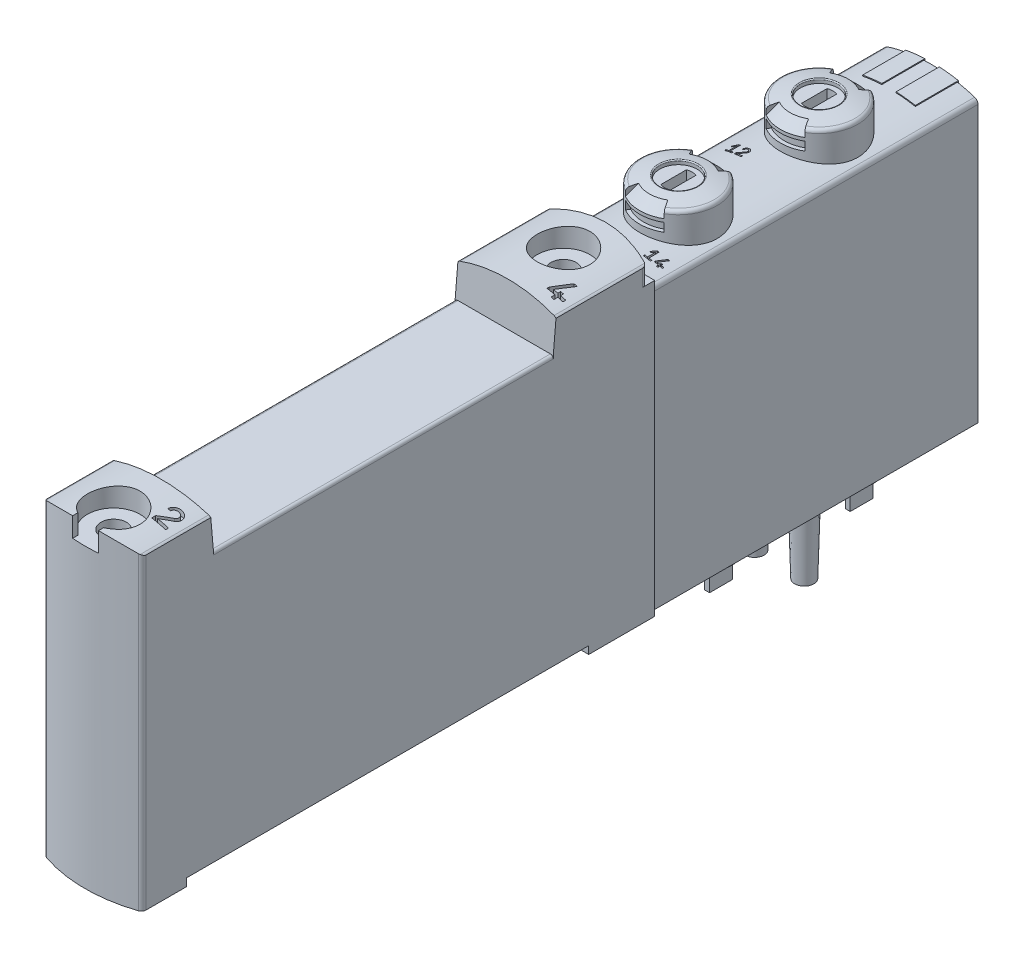
SolidWorks part; units mm, degrees
ref_plane "Front Plane" through (0, 0, 0) normal (0, 0, 1) x (1, 0, 0)
ref_plane "Top Plane" through (0, 0, 0) normal (0, 1, 0) x (1, 0, 0)
ref_plane "Right Plane" through (0, 0, 0) normal (1, 0, 0) x (0, 0, -1)
ref_plane "Plane1" through (0, 0, -23.2) normal (0, 0, 1) x (1, 0, 0)
sketch "Sketch1" plane through (0, 0, -23.2) normal (0, 0, 1) x (1, 0, 0)
  line L0 (-4.9, 29.2163) -> (-4.9, 0)
  line L1 (-4.9, 0) -> (4.9, 0)
  line L2 (4.9, 0) -> (4.9, 29.2163)
  arc A0 (4.9, 29.2163) -> (4.5517, 29.6927) centre (4.4, 29.2163) ccw
  arc A1 (4.5517, 29.6927) -> (-4.5517, 29.6927) centre (0, 15.4) ccw
  arc A2 (-4.5517, 29.6927) -> (-4.9, 29.2163) centre (-4.4, 29.2163) ccw
extrude "Boss-Extrude1" add sketch "Sketch1" along normal blind 34
ref_plane "Plane2" through (0, 0, 0) normal (1, 0, 0) x (0, 0, -1)
sketch "Sketch2" plane through (0, 0, 0) normal (1, 0, 0) x (0, 0, -1)
  line L0 (-10.88, 0.4) -> (-10.88, 0)
  line L1 (-10.88, 0) -> (23.22, 0)
  line L2 (23.22, 0) -> (23.22, 0.4)
  line L3 (23.22, 0.4) -> (-10.88, 0.4)
extrude "Cut-Extrude1" cut sketch "Sketch2" against normal blind 6 and the other way blind 6
ref_plane "Plane3" through (0, 0, 0) normal (0, 1, 0) x (1, 0, 0)
sketch "Sketch3" plane through (0, 0, 0) normal (0, 1, 0) x (1, 0, 0)
  line L0 (-3.15, 2.4653) -> (-3.15, -2.4653)
  line L1 (3.15, -2.4653) -> (3.15, 2.4653)
  arc A0 (-3.15, -2.4653) -> (3.15, -2.4653) centre (0, 0) ccw
  arc A1 (3.15, 2.4653) -> (-3.15, 2.4653) centre (0, 0) ccw
extrude "Cut-Extrude2" cut sketch "Sketch3" along normal blind 1.9
ref_plane "Plane4" through (0, 0, 0) normal (0, 1, 0) x (1, 0, 0)
sketch "Sketch4" plane through (0, 0, 0) normal (0, 1, 0) x (1, 0, 0)
  line L0 (-3.15, 17.1653) -> (-3.15, 12.2347)
  line L1 (3.15, 12.2347) -> (3.15, 17.1653)
  arc A0 (-3.15, 12.2347) -> (3.15, 12.2347) centre (0, 14.7) ccw
  arc A1 (3.15, 17.1653) -> (-3.15, 17.1653) centre (0, 14.7) ccw
extrude "Cut-Extrude3" cut sketch "Sketch4" along normal blind 1.9
ref_plane "Plane5" through (0, 0, 0) normal (1, 0, 0) x (0, 0, -1)
sketch "Sketch5" plane through (0, 0, 0) normal (1, 0, 0) x (0, 0, -1)
  line L0 (0, 2.1) -> (3.05, 2.1)
  line L1 (3.05, 2.1) -> (3.05, 1.1)
  line L2 (3.05, 1.1) -> (2.25, 1.1)
  line L3 (2.25, 1.1) -> (2.25, -1.4)
  line L4 (2.25, -1.4) -> (2.65, -1.4)
  line L5 (2.65, -1.4) -> (2.65, -1.72)
  line L6 (2.65, -1.72) -> (2.4306, -2.1)
  line L7 (2.4306, -2.1) -> (0, -2.1)
  line L8 (0, -2.1) -> (0, 2.1)
  line L9 (0, -2.1) -> (0, 2.1) construction
revolve "Revolve1" add sketch "Sketch5" angle 360 about L9 reverse direction yes
ref_plane "Plane6" through (0, 0, 0) normal (1, 0, 0) x (0, 0, -1)
sketch "Sketch6" plane through (0, 0, 0) normal (1, 0, 0) x (0, 0, -1)
  line L0 (14.7, 2.1) -> (17.75, 2.1)
  line L1 (17.75, 2.1) -> (17.75, 1.1)
  line L2 (17.75, 1.1) -> (16.95, 1.1)
  line L3 (16.95, 1.1) -> (16.95, -1.4)
  line L4 (16.95, -1.4) -> (17.35, -1.4)
  line L5 (17.35, -1.4) -> (17.35, -1.72)
  line L6 (17.35, -1.72) -> (17.1306, -2.1)
  line L7 (17.1306, -2.1) -> (14.7, -2.1)
  line L8 (14.7, -2.1) -> (14.7, 2.1)
  line L9 (14.7, -2.1) -> (14.7, 2.1) construction
revolve "Revolve2" add sketch "Sketch6" angle 360 about L9 reverse direction yes
ref_plane "Plane7" through (0, 0, -7.35) normal (0, 0, 1) x (1, 0, 0)
sketch "Sketch7" plane through (0, 0, -7.35) normal (0, 0, 1) x (1, 0, 0)
  line L0 (2.6, 0.4) -> (3.8, 0.4)
  line L1 (3.8, 0.4) -> (3.6, -6.9)
  line L2 (2.6, -7.0623) -> (2.6, 0.4)
  line L3 (2.6, -7.0623) -> (2.6, 0.4) construction
  arc A0 (3.6, -6.9) -> (2.6, -7.0623) centre (2.6, -3.9) cw
revolve "Revolve3" add sketch "Sketch7" angle 360 about L3 reverse direction yes
ref_plane "Plane8" through (0, 0, -7.35) normal (0, 0, 1) x (1, 0, 0)
sketch "Sketch8" plane through (0, 0, -7.35) normal (0, 0, 1) x (1, 0, 0)
  line L0 (-2.6, 0.4) -> (-1.4, 0.4)
  line L1 (-1.4, 0.4) -> (-1.6, -6.9)
  line L2 (-2.6, -7.0623) -> (-2.6, 0.4)
  line L3 (-2.6, -7.0623) -> (-2.6, 0.4) construction
  arc A0 (-1.6, -6.9) -> (-2.6, -7.0623) centre (-2.6, -3.9) cw
revolve "Revolve4" add sketch "Sketch8" angle 360 about L3 reverse direction yes
ref_plane "Plane9" through (0, -2.1, 0) normal (0, -1, 0) x (-1, 0, 0)
sketch "Sketch9" plane through (0, -2.1, 0) normal (0, -1, 0) x (-1, 0, 0)
  line L0 (-1.25, -1.2) -> (-0.75, -1.2)
  line L1 (-0.75, -1.2) -> (-0.75, 1.2)
  line L2 (-0.75, 1.2) -> (-1.25, 1.2)
  line L3 (-1.25, 1.2) -> (-1.25, -1.2)
extrude "Boss-Extrude2" add sketch "Sketch9" along normal blind 2.5
ref_plane "Plane10" through (0, -2.1, 0) normal (0, -1, 0) x (-1, 0, 0)
sketch "Sketch10" plane through (0, -2.1, 0) normal (0, -1, 0) x (-1, 0, 0)
  line L0 (0.75, -1.2) -> (1.25, -1.2)
  line L1 (1.25, -1.2) -> (1.25, 1.2)
  line L2 (1.25, 1.2) -> (0.75, 1.2)
  line L3 (0.75, 1.2) -> (0.75, -1.2)
extrude "Boss-Extrude3" add sketch "Sketch10" along normal blind 2.5
ref_plane "Plane11" through (0, -2.1, 0) normal (0, -1, 0) x (-1, 0, 0)
sketch "Sketch11" plane through (0, -2.1, 0) normal (0, -1, 0) x (-1, 0, 0)
  line L0 (-1.25, 13.5) -> (-0.75, 13.5)
  line L1 (-0.75, 13.5) -> (-0.75, 15.9)
  line L2 (-0.75, 15.9) -> (-1.25, 15.9)
  line L3 (-1.25, 15.9) -> (-1.25, 13.5)
extrude "Boss-Extrude4" add sketch "Sketch11" along normal blind 2.5
ref_plane "Plane12" through (0, -2.1, 0) normal (0, -1, 0) x (-1, 0, 0)
sketch "Sketch12" plane through (0, -2.1, 0) normal (0, -1, 0) x (-1, 0, 0)
  line L0 (0.75, 13.5) -> (1.25, 13.5)
  line L1 (1.25, 13.5) -> (1.25, 15.9)
  line L2 (1.25, 15.9) -> (0.75, 15.9)
  line L3 (0.75, 15.9) -> (0.75, 13.5)
extrude "Boss-Extrude5" add sketch "Sketch12" along normal blind 2.5
ref_plane "Plane13" through (0, 0, 0) normal (1, 0, 0) x (0, 0, -1)
sketch "Sketch13" plane through (0, 0, 0) normal (1, 0, 0) x (0, 0, -1)
  line L0 (-3.2, 33.13) -> (-1.25, 33.13)
  line L1 (-1.25, 33.13) -> (-1.25, 33.4583)
  line L2 (0.85, 32.8364) -> (0.85, 28.4)
  line L3 (0.85, 28.4) -> (-3.2, 28.4)
  line L4 (-3.2, 28.4) -> (-3.2, 33.13)
  line L5 (-3.2, 28.4) -> (-3.2, 33.7) construction
  arc A0 (-1.25, 33.4583) -> (-1.1362, 33.5574) centre (-1.15, 33.4583) cw
  arc A1 (-1.1362, 33.5574) -> (0.55, 33.2237) centre (-3.2, 18.7) cw
  arc A2 (0.55, 33.2237) -> (0.85, 32.8364) centre (0.45, 32.8364) cw
revolve "Revolve5" add sketch "Sketch13" angle 360 about L5 reverse direction yes
ref_plane "Plane14" through (0, 0, 0) normal (1, 0, 0) x (0, 0, -1)
sketch "Sketch14" plane through (0, 0, 0) normal (1, 0, 0) x (0, 0, -1)
  line L0 (11.5, 33.13) -> (13.45, 33.13)
  line L1 (13.45, 33.13) -> (13.45, 33.4583)
  line L2 (15.55, 32.8364) -> (15.55, 28.4)
  line L3 (15.55, 28.4) -> (11.5, 28.4)
  line L4 (11.5, 28.4) -> (11.5, 33.13)
  line L5 (11.5, 28.4) -> (11.5, 33.7) construction
  arc A0 (13.45, 33.4583) -> (13.5638, 33.5574) centre (13.55, 33.4583) cw
  arc A1 (13.5638, 33.5574) -> (15.25, 33.2237) centre (11.5, 18.7) cw
  arc A2 (15.25, 33.2237) -> (15.55, 32.8364) centre (15.15, 32.8364) cw
revolve "Revolve6" add sketch "Sketch14" angle 360 about L5 reverse direction yes
ref_plane "Plane15" through (0, 0, 0) normal (1, 0, 0) x (0, 0, -1)
sketch "Sketch15" plane through (0, 0, 0) normal (1, 0, 0) x (0, 0, -1)
  line L0 (-0.47, 33.7) -> (0.9, 32.33)
  line L1 (0.9, 32.33) -> (0.9, 32.05)
  line L2 (0.9, 32.05) -> (0.45, 32.05)
  line L3 (0.45, 32.05) -> (0.45, 31.15)
  line L4 (0.45, 31.15) -> (0.9, 31.15)
  line L5 (0.9, 31.15) -> (0.9, 30.5)
  line L6 (0.9, 30.5) -> (1.3, 30.5)
  line L7 (1.3, 30.5) -> (1.3, 33.7)
  line L8 (1.3, 33.7) -> (-0.47, 33.7)
  line L9 (-3.2, 30.5) -> (-3.2, 33.7) construction
revolve "Cut-Revolve1" cut sketch "Sketch15" angle 30 about L9 other way angle 30 reverse direction yes
ref_plane "Plane16" through (0, 0, 0) normal (1, 0, 0) x (0, 0, -1)
sketch "Sketch16" plane through (0, 0, 0) normal (1, 0, 0) x (0, 0, -1)
  line L0 (-7.7, 30.5) -> (-7.3, 30.5)
  line L1 (-7.3, 30.5) -> (-7.3, 31.15)
  line L2 (-7.3, 31.15) -> (-6.85, 31.15)
  line L3 (-6.85, 31.15) -> (-6.85, 32.05)
  line L4 (-6.85, 32.05) -> (-7.3, 32.05)
  line L5 (-7.3, 32.05) -> (-7.3, 32.33)
  line L6 (-7.3, 32.33) -> (-5.93, 33.7)
  line L7 (-5.93, 33.7) -> (-7.7, 33.7)
  line L8 (-7.7, 33.7) -> (-7.7, 30.5)
  line L9 (-3.2, 33.7) -> (-3.2, 30.5) construction
revolve "Cut-Revolve2" cut sketch "Sketch16" angle 30 about L9 other way angle 30 reverse direction yes
ref_plane "Plane17" through (0, 33.13, 0) normal (0, 1, 0) x (1, 0, 0)
sketch "Sketch17" plane through (0, 33.13, 0) normal (0, 1, 0) x (1, 0, 0)
  line L0 (0.5, -4.5344) -> (0.5, -1.8656)
  line L1 (-0.5, -1.8656) -> (-0.5, -4.5344)
  arc A0 (-0.5, -4.5344) -> (0.5, -4.5344) centre (0, -3.2) ccw
  arc A1 (0.5, -1.8656) -> (-0.5, -1.8656) centre (0, -3.2) ccw
extrude "Cut-Extrude4" cut sketch "Sketch17" against normal blind 1.7
ref_plane "Plane18" through (0, 0, 0) normal (1, 0, 0) x (0, 0, -1)
sketch "Sketch18" plane through (0, 0, 0) normal (1, 0, 0) x (0, 0, -1)
  line L0 (14.23, 33.7) -> (15.6, 32.33)
  line L1 (15.6, 32.33) -> (15.6, 32.05)
  line L2 (15.6, 32.05) -> (15.15, 32.05)
  line L3 (15.15, 32.05) -> (15.15, 31.15)
  line L4 (15.15, 31.15) -> (15.6, 31.15)
  line L5 (15.6, 31.15) -> (15.6, 30.5)
  line L6 (15.6, 30.5) -> (16, 30.5)
  line L7 (16, 30.5) -> (16, 33.7)
  line L8 (16, 33.7) -> (14.23, 33.7)
  line L9 (11.5, 30.5) -> (11.5, 33.7) construction
revolve "Cut-Revolve3" cut sketch "Sketch18" angle 30 about L9 other way angle 30 reverse direction yes
ref_plane "Plane19" through (0, 0, 0) normal (1, 0, 0) x (0, 0, -1)
sketch "Sketch19" plane through (0, 0, 0) normal (1, 0, 0) x (0, 0, -1)
  line L0 (7, 30.5) -> (7.4, 30.5)
  line L1 (7.4, 30.5) -> (7.4, 31.15)
  line L2 (7.4, 31.15) -> (7.85, 31.15)
  line L3 (7.85, 31.15) -> (7.85, 32.05)
  line L4 (7.85, 32.05) -> (7.4, 32.05)
  line L5 (7.4, 32.05) -> (7.4, 32.33)
  line L6 (7.4, 32.33) -> (8.77, 33.7)
  line L7 (8.77, 33.7) -> (7, 33.7)
  line L8 (7, 33.7) -> (7, 30.5)
  line L9 (11.5, 33.7) -> (11.5, 30.5) construction
revolve "Cut-Revolve4" cut sketch "Sketch19" angle 30 about L9 other way angle 30 reverse direction yes
ref_plane "Plane20" through (0, 33.13, 0) normal (0, 1, 0) x (1, 0, 0)
sketch "Sketch20" plane through (0, 33.13, 0) normal (0, 1, 0) x (1, 0, 0)
  line L0 (0.5, 10.1656) -> (0.5, 12.8344)
  line L1 (-0.5, 12.8344) -> (-0.5, 10.1656)
  arc A0 (-0.5, 10.1656) -> (0.5, 10.1656) centre (0, 11.5) ccw
  arc A1 (0.5, 12.8344) -> (-0.5, 12.8344) centre (0, 11.5) ccw
extrude "Cut-Extrude5" cut sketch "Sketch20" against normal blind 1.7
ref_plane "Plane21" through (0, 0, -23.3) normal (0, 0, 1) x (1, 0, 0)
sketch "Sketch21" plane through (0, 0, -23.3) normal (0, 0, 1) x (1, 0, 0)
  line L0 (0.75, 30.4814) -> (0.75, 27)
  line L1 (0.75, 27) -> (2.75, 27)
  line L2 (2.75, 27) -> (2.75, 30.2475)
  arc A0 (2.75, 30.2475) -> (0.75, 30.4814) centre (0, 15.4) ccw
extrude "Boss-Extrude6" add sketch "Sketch21" along normal blind 4.5
ref_plane "Plane22" through (0, 0, -23.3) normal (0, 0, 1) x (1, 0, 0)
sketch "Sketch22" plane through (0, 0, -23.3) normal (0, 0, 1) x (1, 0, 0)
  line L0 (-2.75, 30.2475) -> (-2.75, 27)
  line L1 (-2.75, 27) -> (-0.75, 27)
  line L2 (-0.75, 27) -> (-0.75, 30.4814)
  arc A0 (-0.75, 30.4814) -> (-2.75, 30.2475) centre (0, 15.4) ccw
extrude "Boss-Extrude7" add sketch "Sketch22" along normal blind 4.5
ref_plane "Plane23" through (0, 0, 0) normal (0, 1, 0) x (1, 0, 0)
sketch "Sketch23" plane through (0, 0, 0) normal (0, 1, 0) x (1, 0, 0)
  line L0 (5.125, -63.9426) -> (5.125, -10.8)
  line L1 (5.125, -10.8) -> (-5.125, -10.8)
  line L2 (-5.125, -10.8) -> (-5.125, -63.9426)
  arc A0 (-5.125, -63.9426) -> (-4.7845, -64.4165) centre (-4.625, -63.9426) ccw
  arc A1 (-4.7845, -64.4165) -> (4.7845, -64.4165) centre (0, -50.2) ccw
  arc A2 (4.7845, -64.4165) -> (5.125, -63.9426) centre (4.625, -63.9426) ccw
extrude "Boss-Extrude8" add sketch "Sketch23" along normal blind 33.1
ref_plane "Plane24" through (0, 0, 0) normal (1, 0, 0) x (0, 0, -1)
sketch "Sketch24" plane through (0, 0, 0) normal (1, 0, 0) x (0, 0, -1)
  line L0 (-57.7749, 38.9) -> (-56.9, 28.9)
  line L1 (-56.9, 28.9) -> (-21.4, 28.9)
  line L2 (-21.4, 28.9) -> (-20.5251, 38.9)
  line L3 (-20.5251, 38.9) -> (-57.7749, 38.9)
extrude "Cut-Extrude6" cut sketch "Sketch24" against normal blind 10 and the other way blind 10
ref_plane "Plane25" through (0, 30.4, 0) normal (0, 1, 0) x (1, 0, 0)
sketch "Sketch25" plane through (0, 30.4, 0) normal (0, 1, 0) x (1, 0, 0)
  line L0 (-5.125, -8.8) -> (-5.125, -12.0574)
  line L1 (5.125, -12.0574) -> (5.125, -8.8)
  line L2 (5.125, -8.8) -> (-5.125, -8.8)
  arc A0 (-5.125, -12.0574) -> (-4.7845, -11.5835) centre (-4.625, -12.0574) cw
  arc A1 (-4.7845, -11.5835) -> (4.7845, -11.5835) centre (0, -25.8) cw
  arc A2 (4.7845, -11.5835) -> (5.125, -12.0574) centre (4.625, -12.0574) cw
extrude "Cut-Extrude7" cut sketch "Sketch25" along normal blind 10
ref_plane "Plane26" through (0, 0, 0) normal (1, 0, 0) x (0, 0, -1)
sketch "Sketch26" plane through (0, 0, 0) normal (1, 0, 0) x (0, 0, -1)
  line L0 (-59.7, -0.2) -> (-17.7, -0.2)
  line L1 (-17.7, -0.2) -> (-17.7, 0.8)
  line L2 (-17.7, 0.8) -> (-59.7, 0.8)
  line L3 (-59.7, 0.8) -> (-59.7, -0.2)
extrude "Cut-Extrude8" cut sketch "Sketch26" against normal blind 10 and the other way blind 10
ref_plane "Plane27" through (0, 0, 10.8) normal (0, 0, 1) x (1, 0, 0)
sketch "Sketch27" plane through (0, 0, 10.8) normal (0, 0, 1) x (1, 0, 0)
  line L0 (-5.25, 35.1) -> (-5.25, 31.7999)
  line L1 (5.25, 31.7999) -> (5.25, 35.1)
  line L2 (5.25, 35.1) -> (-5.25, 35.1)
  arc A0 (-5.25, 31.7999) -> (-4.9138, 32.2723) centre (-4.75, 31.7999) cw
  arc A1 (-4.9138, 32.2723) -> (4.9138, 32.2723) centre (0, 18.1) cw
  arc A2 (4.9138, 32.2723) -> (5.25, 31.7999) centre (4.75, 31.7999) cw
extrude "Cut-Extrude9" cut sketch "Sketch27" along normal blind 55
ref_plane "Plane28" through (0, 0, 21.4) normal (0, 0, 1) x (1, 0, 0)
sketch "Sketch28" plane through (0, 0, 21.4) normal (0, 0, 1) x (1, 0, 0)
  line L0 (-4.825, 28.9) -> (4.825, 28.9)
  line L1 (5.125, 28.6) -> (5.125, 33.6)
  line L2 (5.125, 33.6) -> (-5.125, 33.6)
  line L3 (-5.125, 33.6) -> (-5.125, 28.6)
  arc A0 (-5.125, 28.6) -> (-4.825, 28.9) centre (-4.825, 28.6) cw
  arc A1 (4.825, 28.9) -> (5.125, 28.6) centre (4.825, 28.6) cw
extrude "Cut-Extrude10" cut sketch "Sketch28" along normal blind 35.5
ref_plane "Plane29" through (0, 33.1, 0) normal (0, 1, 0) x (1, 0, 0)
sketch "Sketch29" plane through (0, 33.1, 0) normal (0, 1, 0) x (1, 0, 0)
  line L0 (-1.35, -64.5958) -> (-1.35, -66)
  line L1 (-1.35, -66) -> (1.35, -66)
  line L2 (1.35, -66) -> (1.35, -64.5958)
  arc A0 (1.35, -64.5958) -> (-1.35, -64.5958) centre (0, -62.2) ccw
extrude "Cut-Extrude11" cut sketch "Sketch29" against normal blind 2.1 and the other way blind 2.1
ref_plane "Plane30" through (0, 0, 0) normal (1, 0, 0) x (0, 0, -1)
sketch "Sketch30" plane through (0, 0, 0) normal (1, 0, 0) x (0, 0, -1)
  line L0 (-62.2, 31) -> (-60.875, 31)
  line L1 (-60.875, 31) -> (-60.875, 0)
  line L2 (-60.875, 0) -> (-62.2, 0)
  line L3 (-62.2, 0) -> (-62.2, 31)
  line L4 (-62.2, 0) -> (-62.2, 31) construction
revolve "Cut-Revolve5" cut sketch "Sketch30" angle 360 about L4 reverse direction yes
ref_plane "Plane31" through (0, 0, 0) normal (1, 0, 0) x (0, 0, -1)
sketch "Sketch31" plane through (0, 0, 0) normal (1, 0, 0) x (0, 0, -1)
  line L0 (-15.2, 33.2) -> (-12.45, 33.2)
  line L1 (-12.45, 33.2) -> (-12.45, 31)
  line L2 (-12.45, 31) -> (-13.875, 31)
  line L3 (-13.875, 31) -> (-13.875, 0)
  line L4 (-13.875, 0) -> (-15.2, 0)
  line L5 (-15.2, 0) -> (-15.2, 33.2)
  line L6 (-15.2, 0) -> (-15.2, 33.2) construction
revolve "Cut-Revolve6" cut sketch "Sketch31" angle 360 about L6 reverse direction yes
ref_plane "Plane32" through (0, 0, 0) normal (1, 0, 0) x (0, 0, -1)
sketch "Sketch32" plane through (0, 0, 0) normal (1, 0, 0) x (0, 0, -1)
  line L0 (-40.2, 9.8) -> (-38.1, 9.8)
  line L1 (-38.1, 9.8) -> (-38.1, 1.8)
  line L2 (-38.1, 1.8) -> (-37.4, 1.8)
  line L3 (-37.4, 1.8) -> (-37.4, 0.8)
  line L4 (-37.4, 0.8) -> (-40.2, 0.8)
  line L5 (-40.2, 0.8) -> (-40.2, 9.8)
  line L6 (-40.2, 0.8) -> (-40.2, 9.8) construction
revolve "Cut-Revolve7" cut sketch "Sketch32" angle 360 about L6 reverse direction yes
ref_plane "Plane33" through (-1.55, 0, 0) normal (1, 0, 0) x (0, 0, -1)
sketch "Sketch33" plane through (-1.55, 0, 0) normal (1, 0, 0) x (0, 0, -1)
  line L0 (-29.1, 9.8) -> (-27, 9.8)
  line L1 (-27, 9.8) -> (-27, 1.8)
  line L2 (-27, 1.8) -> (-26.3, 1.8)
  line L3 (-26.3, 1.8) -> (-26.3, 0.8)
  line L4 (-26.3, 0.8) -> (-29.1, 0.8)
  line L5 (-29.1, 0.8) -> (-29.1, 9.8)
  line L6 (-29.1, 0.8) -> (-29.1, 9.8) construction
revolve "Cut-Revolve8" cut sketch "Sketch33" angle 360 about L6 reverse direction yes
ref_plane "Plane34" through (-1.55, 0, 0) normal (1, 0, 0) x (0, 0, -1)
sketch "Sketch34" plane through (-1.55, 0, 0) normal (1, 0, 0) x (0, 0, -1)
  line L0 (-46.1, 9.8) -> (-44, 9.8)
  line L1 (-44, 9.8) -> (-44, 1.8)
  line L2 (-44, 1.8) -> (-43.3, 1.8)
  line L3 (-43.3, 1.8) -> (-43.3, 0.8)
  line L4 (-43.3, 0.8) -> (-46.1, 0.8)
  line L5 (-46.1, 0.8) -> (-46.1, 9.8)
  line L6 (-46.1, 0.8) -> (-46.1, 9.8) construction
revolve "Cut-Revolve9" cut sketch "Sketch34" angle 360 about L6 reverse direction yes
ref_plane "Plane35" through (1.55, 0, 0) normal (1, 0, 0) x (0, 0, -1)
sketch "Sketch35" plane through (1.55, 0, 0) normal (1, 0, 0) x (0, 0, -1)
  line L0 (-34.3, 9.8) -> (-32.2, 9.8)
  line L1 (-32.2, 9.8) -> (-32.2, 1.8)
  line L2 (-32.2, 1.8) -> (-31.5, 1.8)
  line L3 (-31.5, 1.8) -> (-31.5, 0.8)
  line L4 (-31.5, 0.8) -> (-34.3, 0.8)
  line L5 (-34.3, 0.8) -> (-34.3, 9.8)
  line L6 (-34.3, 0.8) -> (-34.3, 9.8) construction
revolve "Cut-Revolve10" cut sketch "Sketch35" angle 360 about L6 reverse direction yes
ref_plane "Plane36" through (1.55, 0, 0) normal (1, 0, 0) x (0, 0, -1)
sketch "Sketch36" plane through (1.55, 0, 0) normal (1, 0, 0) x (0, 0, -1)
  line L0 (-51.3, 9.8) -> (-49.2, 9.8)
  line L1 (-49.2, 9.8) -> (-49.2, 1.8)
  line L2 (-49.2, 1.8) -> (-48.5, 1.8)
  line L3 (-48.5, 1.8) -> (-48.5, 0.8)
  line L4 (-48.5, 0.8) -> (-51.3, 0.8)
  line L5 (-51.3, 0.8) -> (-51.3, 9.8)
  line L6 (-51.3, 0.8) -> (-51.3, 9.8) construction
revolve "Cut-Revolve11" cut sketch "Sketch36" angle 360 about L6 reverse direction yes
ref_plane "Plane37" through (0, 33.1, 0) normal (0, 1, 0) x (1, 0, 0)
sketch "Sketch37" plane through (0, 33.1, 0) normal (0, 1, 0) x (1, 0, 0)
  line L0 (-3.3985, 5.738) -> (-3.2978, 5.6676)
  line L1 (-3.2978, 5.6676) -> (-3.075, 5.9858)
  line L2 (-3.075, 5.9858) -> (-3.075, 5.15)
  line L3 (-3.075, 5.15) -> (-3.375, 5.15)
  line L4 (-3.375, 5.15) -> (-3.375, 5)
  line L5 (-3.375, 5) -> (-2.625, 5)
  line L6 (-2.625, 5) -> (-2.625, 5.15)
  line L7 (-2.625, 5.15) -> (-2.925, 5.15)
  line L8 (-2.925, 5.15) -> (-2.925, 6.2)
  line L9 (-2.925, 6.2) -> (-3.075, 6.2)
  line L10 (-3.075, 6.2) -> (-3.3985, 5.738)
extrude "Cut-Extrude12" cut sketch "Sketch37" against normal blind 3.5 and the other way blind 3.5
ref_plane "Plane38" through (0, 33.1, 0) normal (0, 1, 0) x (1, 0, 0)
sketch "Sketch38" plane through (0, 33.1, 0) normal (0, 1, 0) x (1, 0, 0)
  line L0 (-2.3625, 5.8375) -> (-2.2125, 5.8375)
  line L1 (-1.8546, 5.6826) -> (-2.3625, 5.2057)
  line L2 (-2.3625, 5.2057) -> (-2.3625, 5)
  line L3 (-2.3625, 5) -> (-1.6375, 5)
  line L4 (-1.6375, 5) -> (-1.6375, 5.15)
  line L5 (-1.6375, 5.15) -> (-2.2027, 5.15)
  line L6 (-2.2027, 5.15) -> (-1.7519, 5.5732)
  arc A0 (-2.2125, 5.8375) -> (-1.8546, 5.6826) centre (-2, 5.8375) cw
  arc A1 (-1.7519, 5.5732) -> (-2.3625, 5.8375) centre (-2, 5.8375) ccw
extrude "Cut-Extrude13" cut sketch "Sketch38" against normal blind 3.5 and the other way blind 3.5
ref_plane "Plane39" through (0, 33.1, 0) normal (0, 1, 0) x (1, 0, 0)
sketch "Sketch39" plane through (0, 33.1, 0) normal (0, 1, 0) x (1, 0, 0)
  line L0 (2.1015, -8.262) -> (2.2022, -8.3324)
  line L1 (2.2022, -8.3324) -> (2.425, -8.0142)
  line L2 (2.425, -8.0142) -> (2.425, -8.85)
  line L3 (2.425, -8.85) -> (2.125, -8.85)
  line L4 (2.125, -8.85) -> (2.125, -9)
  line L5 (2.125, -9) -> (2.875, -9)
  line L6 (2.875, -9) -> (2.875, -8.85)
  line L7 (2.875, -8.85) -> (2.575, -8.85)
  line L8 (2.575, -8.85) -> (2.575, -7.8)
  line L9 (2.575, -7.8) -> (2.425, -7.8)
  line L10 (2.425, -7.8) -> (2.1015, -8.262)
extrude "Cut-Extrude14" cut sketch "Sketch39" against normal blind 3.5 and the other way blind 3.5
ref_plane "Plane40" through (0, 33.1, 0) normal (0, 1, 0) x (1, 0, 0)
sketch "Sketch40" plane through (0, 33.1, 0) normal (0, 1, 0) x (1, 0, 0)
  line L0 (3.085, -8.8) -> (3.5, -8.8)
  line L1 (3.5, -8.8) -> (3.5, -9)
  line L2 (3.5, -9) -> (3.65, -9)
  line L3 (3.65, -9) -> (3.65, -8.8)
  line L4 (3.65, -8.8) -> (3.915, -8.8)
  line L5 (3.915, -8.8) -> (3.915, -8.65)
  line L6 (3.915, -8.65) -> (3.65, -8.65)
  line L7 (3.65, -8.65) -> (3.65, -8.5)
  line L8 (3.65, -8.5) -> (3.5, -8.5)
  line L9 (3.5, -8.5) -> (3.5, -8.65)
  line L10 (3.5, -8.65) -> (3.2699, -8.65)
  line L11 (3.2699, -8.65) -> (3.6663, -7.8)
  line L12 (3.6663, -7.8) -> (3.5008, -7.8)
  line L13 (3.5008, -7.8) -> (3.085, -8.6917)
  line L14 (3.085, -8.6917) -> (3.085, -8.8)
extrude "Cut-Extrude15" cut sketch "Sketch40" against normal blind 3.5 and the other way blind 3.5
ref_plane "Plane41" through (0, 33.1, 0) normal (0, 1, 0) x (1, 0, 0)
sketch "Sketch41" plane through (0, 33.1, 0) normal (0, 1, 0) x (1, 0, 0)
  line L0 (2.67, -19.6) -> (3.5, -19.6)
  line L1 (3.5, -19.6) -> (3.5, -20)
  line L2 (3.5, -20) -> (3.8, -20)
  line L3 (3.8, -20) -> (3.8, -19.6)
  line L4 (3.8, -19.6) -> (4.33, -19.6)
  line L5 (4.33, -19.6) -> (4.33, -19.3)
  line L6 (4.33, -19.3) -> (3.8, -19.3)
  line L7 (3.8, -19.3) -> (3.8, -19)
  line L8 (3.8, -19) -> (3.5, -19)
  line L9 (3.5, -19) -> (3.5, -19.3)
  line L10 (3.5, -19.3) -> (3.0399, -19.3)
  line L11 (3.0399, -19.3) -> (3.8326, -17.6)
  line L12 (3.8326, -17.6) -> (3.5016, -17.6)
  line L13 (3.5016, -17.6) -> (2.67, -19.3834)
  line L14 (2.67, -19.3834) -> (2.67, -19.6)
extrude "Cut-Extrude16" cut sketch "Sketch41" against normal blind 1 and the other way blind 1
ref_plane "Plane42" through (0, 33.1, 0) normal (0, 1, 0) x (1, 0, 0)
sketch "Sketch42" plane through (0, 33.1, 0) normal (0, 1, 0) x (1, 0, 0)
  line L0 (2.775, -59.325) -> (3.075, -59.325)
  line L1 (3.7909, -59.6349) -> (2.775, -60.5885)
  line L2 (2.775, -60.5885) -> (2.775, -61)
  line L3 (2.775, -61) -> (4.225, -61)
  line L4 (4.225, -61) -> (4.225, -60.7)
  line L5 (4.225, -60.7) -> (3.0946, -60.7)
  line L6 (3.0946, -60.7) -> (3.9962, -59.8536)
  arc A0 (3.075, -59.325) -> (3.7909, -59.6349) centre (3.5, -59.325) cw
  arc A1 (3.9962, -59.8536) -> (2.775, -59.325) centre (3.5, -59.325) ccw
extrude "Cut-Extrude17" cut sketch "Sketch42" against normal blind 1 and the other way blind 1
